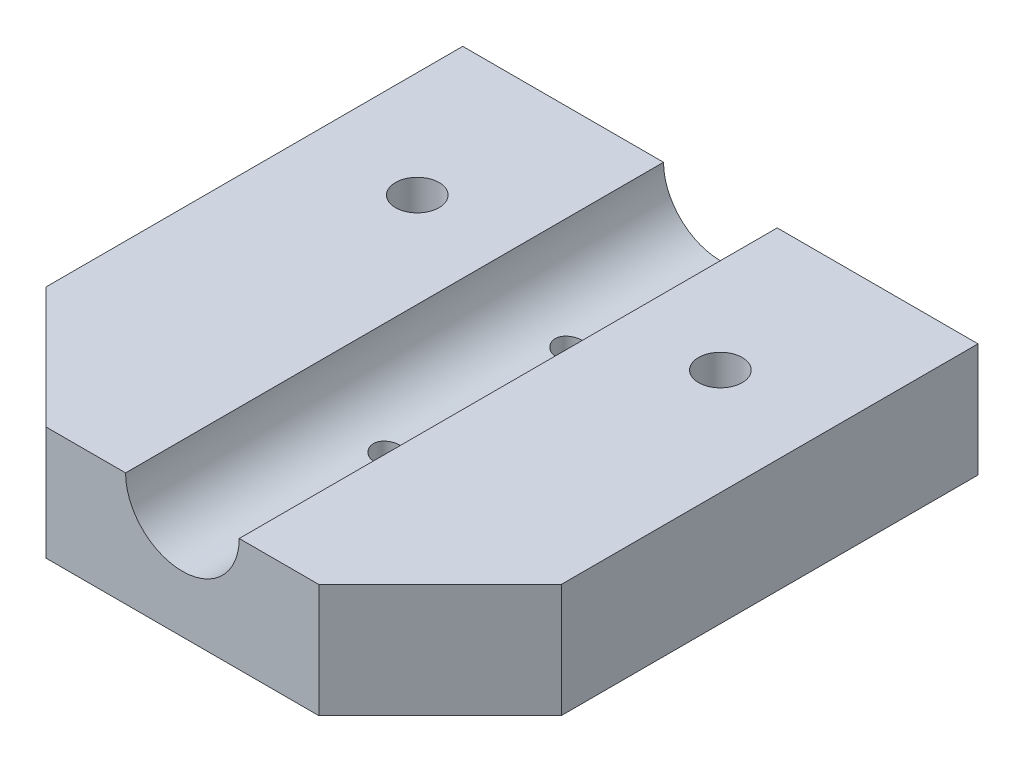
SolidWorks part; units mm, degrees
material "Nylon 6/10"
ref_plane "Front Plane" through (0, 0, 0) normal (0, 0, 1) x (1, 0, 0)
ref_plane "Top Plane" through (0, 0, 0) normal (0, 1, 0) x (1, 0, 0)
ref_plane "Right Plane" through (0, 0, 0) normal (1, 0, 0) x (0, 0, -1)
sketch "Sketch1" plane through (0, 0, 0) normal (0, 1, 0) x (1, 0, 0)
  line L1 (-21.59, -22.5425) -> (21.59, -22.5425)
  line L2 (-21.59, -22.5425) -> (-21.59, 22.5425)
  line L3 (-21.59, 22.5425) -> (21.59, 22.5425)
  line L4 (21.59, -22.5425) -> (21.59, 22.5425)
  line L5 (-21.59, -22.5425) -> (21.59, 22.5425) construction
  line L6 (-21.59, 22.5425) -> (21.59, -22.5425) construction
  point P0 (0, 0)
  dimension "D1" = 45.085
  dimension "D2" = 43.18
extrude "Boss-Extrude1" add sketch "Sketch1" along normal blind 9.525
sketch "Sketch4" plane through (0, 0, 22.5425) normal (0, 0, 1) x (1, 0, 0)
  line L0 (-21.59, 9.525) -> (21.59, 9.525) construction
  circle A0 centre (0, 9.525) radius 4.7625
  dimension "D1" = 9.525
extrude "Cut-Extrude1" cut sketch "Sketch4" against normal through all
hole_wizard "MotorHoles" positions "Sketch3" profile "Sketch2" tap size "#4-40" standard "ANSI Inch"
sketch "Sketch3" plane through (0, 0, 0) normal (0, -1, 0) x (-1, 0, 0)
  line L0 (21.59, -22.5425) -> (-21.59, -22.5425) construction
  line L2 (0, 0) -> (0, -31.1437) construction
  point P0 (-5.715, -19.3675)
  point P2 (5.715, -19.3675)
  point P15 (13.081, 19.6469)
  point P17 (-13.081, 19.6469)
  dimension "D1" = 3.175
  dimension "D2" = 11.43
  dimension "D3" = 39.0144
  dimension "D4" = 7.366
  dimension "D5" = 7.366
cosmetic thread "Hole Thread1"
cosmetic thread "Hole Thread2"
sketch "Sketch2" plane through (5.715, 0, 19.3675) normal (1, 0, 0) x (0, 0, -1)
  line L0 (0, 0) -> (0, 7.0292)
  line L1 (0, 7.0292) -> (1.1303, 6.35)
  line L2 (1.1303, 6.35) -> (1.1303, 0)
  line L5 (1.1303, 0) -> (0, 0)
  line L10 (0, 7.0292) -> (-1.1303, 6.35) construction
  line L11 (0, -6.35) -> (0, 107.95) construction
  dimension "Tap Drill Dia." = 2.2606
  dimension "Tap Drill Depth" = 6.35
  dimension "Drill Angle" = 118
cosmetic thread "Hole Thread5"
cosmetic thread "Hole Thread6"
hole_wizard "CBORE for #6 Socket Head Cap Screw1" positions "Sketch6" profile "Sketch5" counterbore size "#6" standard "ANSI Inch" end condition through all
sketch "Sketch6" plane through (0, 0, 0) normal (0, -1, 0) x (-1, 0, 0)
  line L0 (0, 0) -> (0, 20.3228) construction
  line L2 (-21.59, 22.5425) -> (21.59, 22.5425) construction
  point P0 (-12.7, 9.8425)
  point P2 (12.7, 9.8425)
  dimension "D1" = 25.4
  dimension "D2" = 12.7
sketch "Sketch5" plane through (12.7, 0, -9.8425) normal (1, 0, 0) x (0, 0, -1)
  line L0 (0, 0) -> (0, 9.525)
  line L1 (0, 9.525) -> (1.8288, 9.525)
  line L3 (1.8288, 9.525) -> (1.8288, 3.5052)
  line L4 (1.8288, 3.5052) -> (3.5725, 3.5052)
  line L5 (3.5725, 3.5052) -> (3.5725, 0)
  line L7 (3.5725, 0) -> (0, 0)
  line L11 (0, -6.35) -> (0, 107.95) construction
  dimension "Thru Hole Dia." = 3.6576
  dimension "Thru Hole Depth" = 9.525
  dimension "C'Bore Dia." = 7.145
  dimension "C'Bore Depth" = 3.5052
chamfer "Chamfer1" distance 10.16 angle 45 2 edges at (21.59, 4.7625, 22.5425) (-21.59, 4.7625, 22.5425)
hole_wizard "#4-40 Tapped Hole1" positions "Sketch8" profile "Sketch7" tap size "#4-40" standard "ANSI Inch" end condition through all
sketch "Sketch8" plane through (0, 0, 0) normal (0, -1, 0) x (-1, 0, 0)
  line L0 (0, 0) -> (0, 3.4708) construction
  line L2 (-12.7, 9.8425) -> (12.7, 9.8425) construction
  circle A0 centre (-12.7, 9.8425) radius 1.8288 construction
  circle A1 centre (12.7, 9.8425) radius 1.8288 construction
  circle A2 centre (-12.7, 9.8425) radius 1.8288 construction
  circle A3 centre (12.7, 9.8425) radius 1.8288 construction
  point P0 (0, 9.8425)
  point P2 (0, -5.3975)
  dimension "D1" = 15.24
sketch "Sketch7" plane through (0, 0, -9.8425) normal (1, 0, 0) x (0, 0, -1)
  line L0 (0, 0) -> (0, 9.525)
  line L1 (0, 9.525) -> (1.1303, 9.525)
  line L2 (1.1303, 9.525) -> (1.1303, 0)
  line L5 (1.1303, 0) -> (0, 0)
  line L11 (0, -6.35) -> (0, 107.95) construction
  dimension "Thru Tap Drill Dia." = 2.2606
  dimension "Thru Tap Drill Depth" = 9.525
cosmetic thread "Hole Thread3"
cosmetic thread "Hole Thread4"
chamfer "Chamfer3" [suppressed] distance 5.08 angle 45
